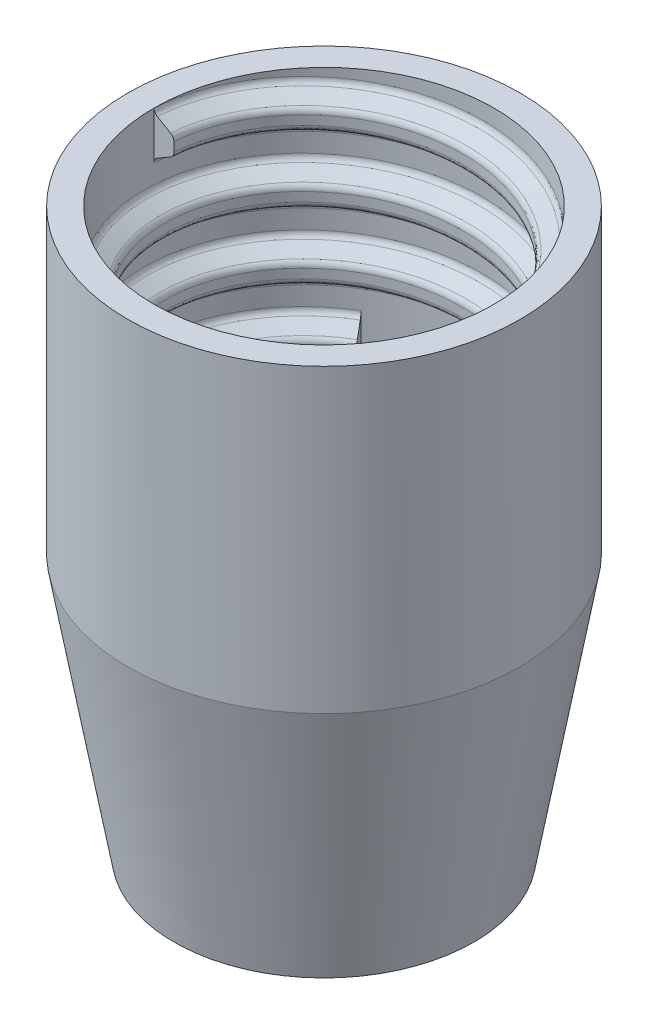
SolidWorks part; units mm, degrees
ref_plane "Front Plane" through (0, 0, 0) normal (0, 0, 1) x (1, 0, 0)
ref_plane "Top Plane" through (0, 0, 0) normal (0, 1, 0) x (1, 0, 0)
ref_plane "Right Plane" through (0, 0, 0) normal (1, 0, 0) x (0, 0, -1)
sketch "Sketch1" plane through (0, 0, 0) normal (0, 1, 0) x (1, 0, 0)
  circle A0 centre (0, 0) radius 15
extrude "Boss-Extrude1" add sketch "Sketch1" along normal blind 20 contours A0
sketch "Sketch2" plane through (0, 20, 0) normal (0, 1, 0) x (1, 0, 0)
  circle A0 centre (0, 0) radius 13
sketch "Sketch10" plane through (0, 20, 0) normal (0, 1, 0) x (1, 0, 0)
  circle A0 centre (0, 0) radius 13
extrude "Cut-Extrude2" cut sketch "Sketch10" against normal blind 20
thread "Thread1" pitch 5.08 method extrude profile "Thread Profile2" start angle 0, offset 0, length 16, pitch 5.08, diameter 26
ref_plane "Plane2" through (-13, 20, 0) normal (0, 0, -1) x (1, 0, 0)
sketch "Thread Profile2" plane through (-13, 20, 0) normal (0, 0, -1) x (1, 0, 0)
  line L0 (0, 0) -> (0, 5.08) construction
  line L1 (0, 0) -> (0, 3.6346)
  line L2 (0.508, 3.6346) -> (1.524, 3.6346) construction
  line L3 (1.524, 2.1681) -> (1.524, 1.4665)
  line L4 (1.27, 2.6081) -> (0.254, 3.1946)
  line L5 (1.27, 1.0265) -> (0.254, 0.4399)
  line L6 (0.508, 0) -> (1.524, 0) construction
  arc A0 (0.254, 3.1946) -> (0, 3.6346) centre (0.508, 3.6346) cw
  arc A1 (0.254, 0.4399) -> (0, 0) centre (0.508, 0) ccw
  arc A2 (1.524, 1.4665) -> (1.27, 1.0265) centre (1.016, 1.4665) cw
  arc A3 (1.524, 2.1681) -> (1.27, 2.6081) centre (1.016, 2.1681) ccw
  point P10 (1.524, 2.4614)
  point P17 (1.524, 1.1732)
  point P18 (0, 3.3413)
  point P19 (0, 0.2933)
  point P20 (0, 0)
  dimension "RootFillet1" = 0.508
  dimension "RootFillet2" = 0.508
  dimension "CrestFillet2" = 0.508
  dimension "CrestFillet1" = 0.508
  dimension "Pitch" = 5.08
  dimension "Angle1" = 30
  dimension "Angle2" = 30
  dimension "a" = 3.048
  dimension "b" = 1.524
  dimension "c" = 1.2882
sketch "Sketch19" plane through (0, 0, 0) normal (0, -1, 0) x (-1, 0, 0)
  circle A0 centre (0, 0) radius 13
  circle A1 centre (0, 0) radius 6.5
sketch "Sketch20" plane through (0, 0, 0) normal (0, -1, 0) x (1, 0, 0)
  circle A0 centre (0, 0) radius 15
extrude "Boss-Extrude3" add sketch "Sketch20" along normal blind 3
extrude "Cut-Extrude3" cut sketch "Sketch19" along normal blind 1.5 contours A1
sketch "Sketch47" plane through (0, -1.5, 0) normal (0, 1, 0) x (1, 0, 0)
  circle A0 centre (0, 0) radius 0.5
extrude "Cut-Extrude10" cut sketch "Sketch47" against normal blind 1.5
sketch "Sketch49" plane through (0, -1.5, 0) normal (0, 1, 0) x (1, 0, 0)
  circle A0 centre (0, 0) radius 0.5
  circle A2 centre (1.67, 0) radius 0.5
  point P3 (0, 0)
sketch "Sketch50" plane through (0, -1.5, 0) normal (0, 1, 0) x (1, 0, 0)
  circle A0 centre (3.33, 0) radius 0.5
sketch "Sketch51" plane through (0, -1.5, 0) normal (0, 1, 0) x (1, 0, 0)
  circle A0 centre (5, 0) radius 0.5
extrude "Cut-Extrude13" cut sketch "Sketch49" against normal blind 1.5
extrude "Cut-Extrude14" cut sketch "Sketch50" against normal blind 1.5
extrude "Cut-Extrude15" cut sketch "Sketch51" against normal blind 1.5
pattern_circular "CirPattern1" count 18 over 360 about axis through (0, -1.5, 0) along (0, 1, 0) of "Cut-Extrude15"
pattern_circular "CirPattern2" count 12 over 360 about axis through (0, -1.5, 0) along (0, 1, 0) of "Cut-Extrude14"
pattern_circular "CirPattern3" count 6 over 360 about axis through (0, -1.5, 0) along (0, 1, 0) of "Cut-Extrude13"
sketch "Sketch52" plane through (0, -3, 0) normal (0, -1, 0) x (-1, 0, 0)
  circle A0 centre (0, 0) radius 15
extrude "Boss-Extrude4" add sketch "Sketch52" along normal blind 20 draft 10
sketch "Sketch54" plane through (0, -23, 0) normal (0, -1, 0) x (1, 0, 0)
  circle A0 centre (0, 0) radius 8
extrude "Cut-Extrude16" cut sketch "Sketch54" against normal blind 20
